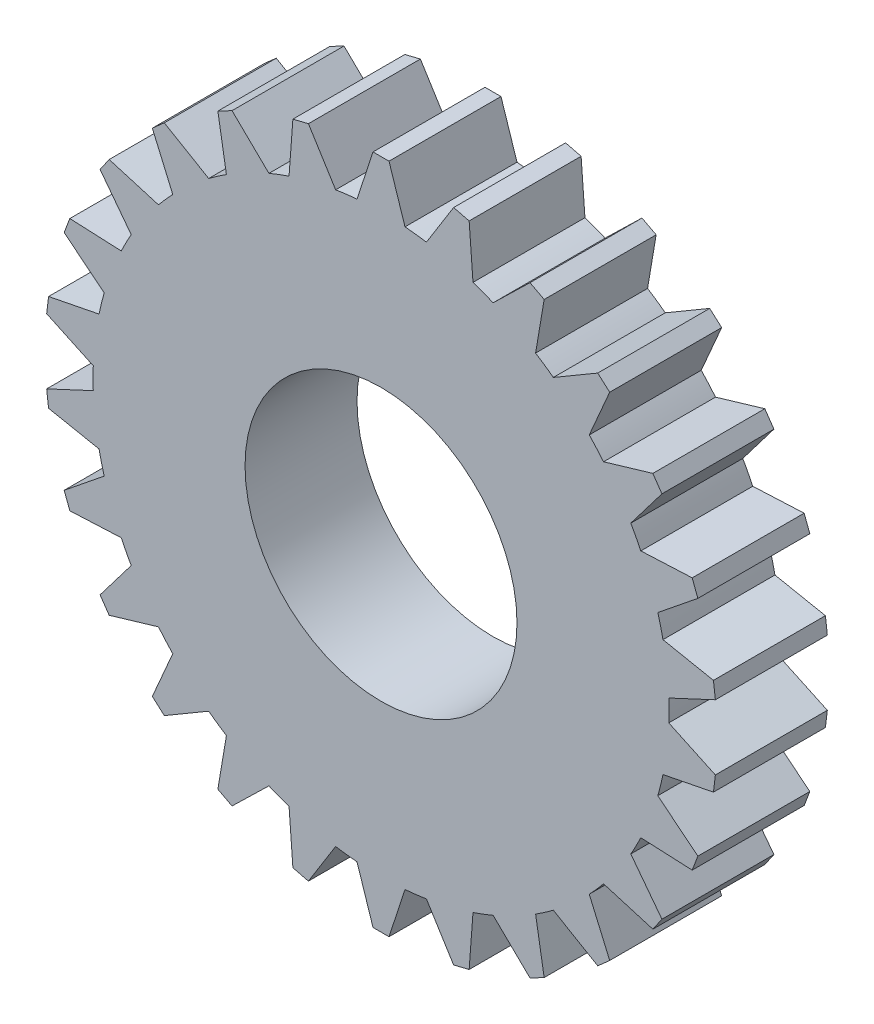
SolidWorks part; units mm, degrees
ref_plane "Front Plane" through (0, 0, 0) normal (0, 0, 1) x (1, 0, 0)
ref_plane "Top Plane" through (0, 0, 0) normal (0, 1, 0) x (1, 0, 0)
ref_plane "Right Plane" through (0, 0, 0) normal (1, 0, 0) x (0, 0, -1)
sketch "Sketch1" plane through (0, 0, 0) normal (0, 0, 1) x (1, 0, 0)
  line L0 (0, 0) -> (0, 21.7596) construction
  line L17 (4.5387, 20.5037) -> (2.8363, 17.7751)
  line L18 (4.5387, 20.5037) -> (5.5097, 20.2643)
  line L19 (5.5097, 20.2643) -> (5.7491, 17.0572)
  line L20 (9.3137, 18.8217) -> (7.0077, 16.5799)
  line L21 (9.3137, 18.8217) -> (10.1991, 18.3569)
  line L22 (10.1991, 18.3569) -> (9.6641, 15.1857)
  line L23 (13.5474, 16.0458) -> (10.7719, 14.421)
  line L24 (13.5474, 16.0458) -> (14.2959, 15.3827)
  line L25 (14.2959, 15.3827) -> (13.0175, 12.4316)
  line L26 (16.9937, 12.3375) -> (13.9101, 11.4241)
  line L27 (-1.5, 17.9374) -> (1.5, 17.9374) construction
  line L28 (-0.5, 20.994) -> (0.5, 20.994)
  line L29 (-0.5, 20.994) -> (-1.5, 17.9374)
  line L30 (0.5, 20.994) -> (1.5, 17.9374)
  line L31 (16.9937, 12.3375) -> (17.5618, 11.5145)
  line L32 (17.5618, 11.5145) -> (15.6143, 8.9551)
  line L33 (19.4525, 7.9121) -> (16.2398, 7.7632)
  line L34 (19.4525, 7.9121) -> (19.8071, 6.9771)
  line L35 (19.8071, 6.9771) -> (17.3037, 4.9582)
  line L36 (20.7807, 3.0269) -> (17.6258, 3.6512)
  line L37 (20.7807, 3.0269) -> (20.9012, 2.0342)
  line L38 (20.9012, 2.0342) -> (17.9874, 0.6731)
  line L39 (20.9012, -2.0342) -> (17.9874, -0.6731)
  line L40 (20.9012, -2.0342) -> (20.7807, -3.0269)
  line L41 (20.7807, -3.0269) -> (17.6258, -3.6512)
  line L42 (19.8071, -6.9771) -> (17.3037, -4.9582)
  line L43 (19.8071, -6.9771) -> (19.4525, -7.9121)
  line L44 (19.4525, -7.9121) -> (16.2398, -7.7632)
  line L45 (17.5618, -11.5145) -> (15.6143, -8.9551)
  line L46 (17.5618, -11.5145) -> (16.9937, -12.3375)
  line L47 (16.9937, -12.3375) -> (13.9101, -11.4241)
  line L48 (14.2959, -15.3827) -> (13.0175, -12.4316)
  line L49 (14.2959, -15.3827) -> (13.5474, -16.0458)
  line L50 (13.5474, -16.0458) -> (10.7719, -14.421)
  line L51 (10.1991, -18.3569) -> (9.6641, -15.1857)
  line L52 (10.1991, -18.3569) -> (9.3137, -18.8217)
  line L53 (9.3137, -18.8217) -> (7.0077, -16.5799)
  line L54 (5.5097, -20.2643) -> (5.7491, -17.0572)
  line L55 (5.5097, -20.2643) -> (4.5387, -20.5037)
  line L56 (4.5387, -20.5037) -> (2.8363, -17.7751)
  line L57 (0.5, -20.994) -> (1.5, -17.9374)
  line L58 (0.5, -20.994) -> (-0.5, -20.994)
  line L59 (-0.5, -20.994) -> (-1.5, -17.9374)
  line L60 (-4.5387, -20.5037) -> (-2.8363, -17.7751)
  line L61 (-4.5387, -20.5037) -> (-5.5097, -20.2643)
  line L62 (-5.5097, -20.2643) -> (-5.7491, -17.0572)
  line L63 (-9.3137, -18.8217) -> (-7.0077, -16.5799)
  line L64 (-9.3137, -18.8217) -> (-10.1991, -18.3569)
  line L65 (-10.1991, -18.3569) -> (-9.6641, -15.1857)
  line L66 (-13.5474, -16.0458) -> (-10.7719, -14.421)
  line L67 (-13.5474, -16.0458) -> (-14.2959, -15.3827)
  line L68 (-14.2959, -15.3827) -> (-13.0175, -12.4316)
  line L69 (-16.9937, -12.3375) -> (-13.9101, -11.4241)
  line L70 (-16.9937, -12.3375) -> (-17.5618, -11.5145)
  line L71 (-17.5618, -11.5145) -> (-15.6143, -8.9551)
  line L72 (-19.4525, -7.9121) -> (-16.2398, -7.7632)
  line L73 (-19.4525, -7.9121) -> (-19.8071, -6.9771)
  line L74 (-19.8071, -6.9771) -> (-17.3037, -4.9582)
  line L75 (-20.7807, -3.0269) -> (-17.6258, -3.6512)
  line L76 (-20.7807, -3.0269) -> (-20.9012, -2.0342)
  line L77 (-20.9012, -2.0342) -> (-17.9874, -0.6731)
  line L78 (-20.9012, 2.0342) -> (-17.9874, 0.6731)
  line L79 (-20.9012, 2.0342) -> (-20.7807, 3.0269)
  line L80 (-20.7807, 3.0269) -> (-17.6258, 3.6512)
  line L81 (-19.8071, 6.9771) -> (-17.3037, 4.9582)
  line L82 (-19.8071, 6.9771) -> (-19.4525, 7.9121)
  line L83 (-19.4525, 7.9121) -> (-16.2398, 7.7632)
  line L84 (-17.5618, 11.5145) -> (-15.6143, 8.9551)
  line L85 (-17.5618, 11.5145) -> (-16.9937, 12.3375)
  line L86 (-16.9937, 12.3375) -> (-13.9101, 11.4241)
  line L87 (-14.2959, 15.3827) -> (-13.0175, 12.4316)
  line L88 (-14.2959, 15.3827) -> (-13.5474, 16.0458)
  line L89 (-13.5474, 16.0458) -> (-10.7719, 14.421)
  line L90 (-10.1991, 18.3569) -> (-9.6641, 15.1857)
  line L91 (-10.1991, 18.3569) -> (-9.3137, 18.8217)
  line L92 (-9.3137, 18.8217) -> (-7.0077, 16.5799)
  line L93 (-5.5097, 20.2643) -> (-5.7491, 17.0572)
  line L94 (-5.5097, 20.2643) -> (-4.5387, 20.5037)
  line L95 (-4.5387, 20.5037) -> (-2.8363, 17.7751)
  circle A0 centre (0, 0) radius 8.5
  arc A17 (-1.5, 17.9374) -> (-2.8363, 17.7751) centre (0, 0) ccw
  arc A18 (-13.5474, 16.0458) -> (-14.2959, 15.3827) centre (0, 0) ccw construction
  arc A19 (2.8363, 17.7751) -> (1.5, 17.9374) centre (0, 0) ccw
  arc A20 (7.0077, 16.5799) -> (5.7491, 17.0572) centre (0, 0) ccw
  arc A21 (10.7719, 14.421) -> (9.6641, 15.1857) centre (0, 0) ccw
  arc A22 (13.9101, 11.4241) -> (13.0175, 12.4316) centre (0, 0) ccw
  arc A23 (16.2398, 7.7632) -> (15.6143, 8.9551) centre (0, 0) ccw
  arc A24 (17.6258, 3.6512) -> (17.3037, 4.9582) centre (0, 0) ccw
  arc A25 (17.9874, -0.6731) -> (17.9874, 0.6731) centre (0, 0) ccw
  arc A26 (17.3037, -4.9582) -> (17.6258, -3.6512) centre (0, 0) ccw
  arc A27 (15.6143, -8.9551) -> (16.2398, -7.7632) centre (0, 0) ccw
  arc A28 (13.0175, -12.4316) -> (13.9101, -11.4241) centre (0, 0) ccw
  arc A29 (9.6641, -15.1857) -> (10.7719, -14.421) centre (0, 0) ccw
  arc A30 (5.7491, -17.0572) -> (7.0077, -16.5799) centre (0, 0) ccw
  arc A31 (1.5, -17.9374) -> (2.8363, -17.7751) centre (0, 0) ccw
  arc A32 (-2.8363, -17.7751) -> (-1.5, -17.9374) centre (0, 0) ccw
  arc A33 (-7.0077, -16.5799) -> (-5.7491, -17.0572) centre (0, 0) ccw
  arc A34 (-10.7719, -14.421) -> (-9.6641, -15.1857) centre (0, 0) ccw
  arc A35 (-13.9101, -11.4241) -> (-13.0175, -12.4316) centre (0, 0) ccw
  arc A36 (-16.2398, -7.7632) -> (-15.6143, -8.9551) centre (0, 0) ccw
  arc A37 (-17.6258, -3.6512) -> (-17.3037, -4.9582) centre (0, 0) ccw
  arc A38 (-17.9874, 0.6731) -> (-17.9874, -0.6731) centre (0, 0) ccw
  arc A39 (-17.3037, 4.9582) -> (-17.6258, 3.6512) centre (0, 0) ccw
  arc A40 (-15.6143, 8.9551) -> (-16.2398, 7.7632) centre (0, 0) ccw
  arc A41 (-13.0175, 12.4316) -> (-13.9101, 11.4241) centre (0, 0) ccw
  arc A42 (-9.6641, 15.1857) -> (-10.7719, 14.421) centre (0, 0) ccw
  arc A43 (-5.7491, 17.0572) -> (-7.0077, 16.5799) centre (0, 0) ccw
  arc A44 (-9.3137, 18.8217) -> (-10.1991, 18.3569) centre (0, 0) ccw construction
  arc A45 (-4.5387, 20.5037) -> (-5.5097, 20.2643) centre (0, 0) ccw construction
  arc A46 (5.5097, 20.2643) -> (-0.5, 20.994) centre (0, 0) ccw construction
  arc A47 (10.1991, 18.3569) -> (9.3137, 18.8217) centre (0, 0) ccw construction
  arc A48 (14.2959, 15.3827) -> (13.5474, 16.0458) centre (0, 0) ccw construction
  arc A49 (17.5618, 11.5145) -> (16.9937, 12.3375) centre (0, 0) ccw construction
  arc A50 (19.8071, 6.9771) -> (19.4525, 7.9121) centre (0, 0) ccw construction
  arc A51 (19.4525, -7.9121) -> (19.8071, -6.9771) centre (0, 0) ccw construction
  arc A52 (16.9937, -12.3375) -> (17.5618, -11.5145) centre (0, 0) ccw construction
  arc A53 (9.3137, -18.8217) -> (10.1991, -18.3569) centre (0, 0) ccw construction
  arc A54 (13.5474, -16.0458) -> (14.2959, -15.3827) centre (0, 0) ccw construction
  arc A55 (-0.5, -20.994) -> (0.5, -20.994) centre (0, 0) ccw construction
  arc A56 (4.5387, -20.5037) -> (5.5097, -20.2643) centre (0, 0) ccw construction
  arc A57 (-5.5097, -20.2643) -> (-4.5387, -20.5037) centre (0, 0) ccw construction
  arc A58 (-10.1991, -18.3569) -> (-9.3137, -18.8217) centre (0, 0) ccw construction
  arc A59 (-14.2959, -15.3827) -> (-13.5474, -16.0458) centre (0, 0) ccw construction
  arc A60 (-19.8071, -6.9771) -> (-19.4525, -7.9121) centre (0, 0) ccw construction
  arc A61 (-20.9012, -2.0342) -> (-20.7807, -3.0269) centre (0, 0) ccw construction
  arc A62 (-20.7807, 3.0269) -> (-20.9012, 2.0342) centre (0, 0) ccw construction
  arc A63 (-19.4525, 7.9121) -> (-19.8071, 6.9771) centre (0, 0) ccw construction
  arc A64 (-16.9937, 12.3375) -> (-17.5618, 11.5145) centre (0, 0) ccw construction
  arc A65 (-17.5618, -11.5145) -> (-16.9937, -12.3375) centre (0, 0) ccw construction
  arc A66 (20.9012, 2.0342) -> (20.7807, 3.0269) centre (0, 0) ccw construction
  arc A67 (20.7807, -3.0269) -> (20.9012, -2.0342) centre (0, 0) ccw construction
  point P41 (0, 0)
  point P112 (0, 0)
  dimension "D1" = 17
  dimension "D2" = 42
  dimension "D3" = 3
  dimension "D6" = 36
  dimension "D4" = 1.5
  dimension "D5" = 1.5
  dimension "D7" = 1
  dimension "D8" = 26
extrude "Boss-Extrude1" add sketch "Sketch1" along normal blind 7 contours A17 | L93 A43 L92 L91 L90 A42 L89 L88 L87 A41 L86 L85 L84 A40 L83 L82 L81 A39 L80 L79 L78 A38 L77 L76 L75 A37 L74 L73 L72 A36 L71 L70 L69 A35 L68 L67 L66 A34 L65 L64 L63 A33 L62 L61 L60 A32 L59 L58 L57 A31 L56 region at (4.8824, 19.8087, 0)
